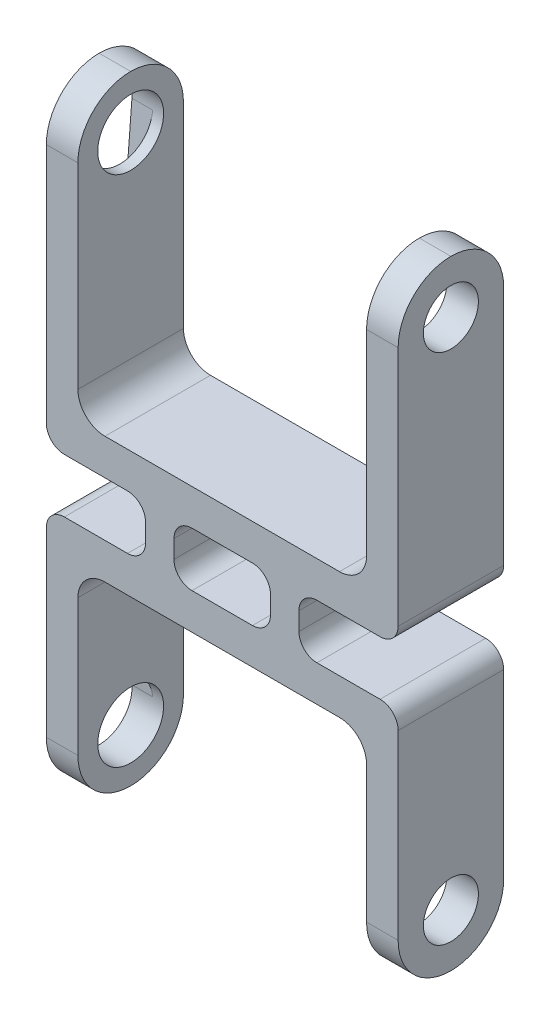
SolidWorks part; units mm, degrees
ref_plane "前视基准面" through (0, 0, 0) normal (0, 0, 1) x (1, 0, 0)
ref_plane "上视基准面" through (0, 0, 0) normal (0, 1, 0) x (1, 0, 0)
ref_plane "右视基准面" through (0, 0, 0) normal (1, 0, 0) x (0, 0, -1)
sketch "草图1" plane through (0, 0, 0) normal (0, 0, 1) x (1, 0, 0)
  line L0 (0, 0) -> (0, -28)
  line L1 (0, -28) -> (3.5, -28)
  line L2 (3.5, -28) -> (3.5, -4)
  line L3 (3.5, -4) -> (35.5, -4)
  line L4 (35.5, -4) -> (35.5, -28)
  line L5 (35.5, -28) -> (39, -28)
  line L6 (39, -28) -> (39, 0)
  line L7 (39, 0) -> (28, 0)
  line L8 (28, 0) -> (28, 6)
  line L9 (28, 6) -> (39, 6)
  line L10 (39, 6) -> (39, 40.6)
  line L11 (39, 40.6) -> (35.5, 40.6)
  line L12 (35.5, 40.6) -> (35.5, 10)
  line L13 (35.5, 10) -> (3.5, 10)
  line L14 (3.5, 10) -> (3.5, 40.6)
  line L15 (3.5, 40.6) -> (0, 40.6)
  line L16 (0, 40.6) -> (0, 6)
  line L17 (0, 6) -> (11, 6)
  line L18 (11, 6) -> (11, 0)
  line L19 (11, 0) -> (0, 0)
  line L20 (0, 3) -> (38, 3) construction
  line L21 (19.5, 4.7421) -> (19.5, 35.9741) construction
  line L22 (11, 3) -> (28, 3) construction
  line L24 (14.15, 0) -> (24.85, 0)
  line L25 (14.15, 0) -> (14.15, 6)
  line L26 (14.15, 6) -> (24.85, 6)
  line L27 (24.85, 0) -> (24.85, 6)
  line L28 (14.15, 0) -> (24.85, 6) construction
  line L29 (14.15, 6) -> (24.85, 0) construction
  point P27 (19.5, 3)
  dimension "D1" = 32
  dimension "D2" = 39
  dimension "D3" = 17
  dimension "D4" = 34.6
  dimension "D5" = 28
  dimension "D6" = 4
  dimension "D7" = 4
  dimension "D8" = 6
  dimension "D9" = 10.7
extrude "凸台-拉伸1" add sketch "草图1" along normal blind 11.7
sketch "草图2" plane through (0, 0, 0) normal (-1, 0, 0) x (0, 0, 1)
  line L0 (5.85, -26) -> (5.85, -9.2381) construction
  line L1 (-6.1344, -22.15) -> (24.0866, -22.15) construction
  line L2 (3.4574, -6.0119) -> (2.2112, -21.8639)
  line L3 (8.2426, -6.0119) -> (9.4888, -21.8639)
  line L4 (0, 0) -> (0, -28)
  line L5 (0, -28) -> (11.7, -28)
  line L6 (11.7, -28) -> (11.7, 0)
  line L7 (11.7, 0) -> (0, 0)
  line L8 (0, 0) -> (0, -28)
  line L9 (0, -28) -> (11.7, -28)
  line L10 (11.7, -28) -> (11.7, 0)
  line L11 (11.7, 0) -> (0, 0)
  line L12 (-23.7504, 6.3) -> (47.2395, 6.3) construction
  line L13 (3.4574, 18.6119) -> (2.2112, 34.4639)
  line L14 (8.2426, 18.6119) -> (9.4888, 34.4639)
  line L16 (11.7, 40.6) -> (0, 40.6) construction
  circle A0 centre (5.85, -22.15) radius 3.65
  arc A1 (8.2426, -6.0119) -> (3.4574, -6.0119) centre (5.85, -6.2) ccw
  arc A2 (8.2426, 18.6119) -> (3.4574, 18.6119) centre (5.85, 18.8) cw
  circle A3 centre (5.85, 34.75) radius 3.65
  point P4 (5.85, -28)
  point P8 (5.85, -22.15)
  point P12 (5.85, -25.8)
  point P16 (5.85, -3.8)
  point P28 (5.85, 38.4)
  dimension "D3" = 22
  dimension "D4" = 4.8
  dimension "D5" = 7.3
  dimension "D2" = 5.85
  dimension "D6" = 5.85
  dimension "D1" = 0
extrude "切除-拉伸1" cut sketch "草图2" against normal blind 18.7 contours A0 region at (0, -22.15, 5.85)
extrude "切除-拉伸2" cut sketch "草图2<3>" against normal blind 2.3 contours L3 A1 L2 A0 region at (0, -12.2589, 5.85)
sketch "草图2<3>" plane through (0, 0, 0) normal (-1, 0, 0) x (0, 0, 1) same geometry as "草图2"
extrude "切除-拉伸3" cut sketch "草图2<4>" against normal blind 15.3 contours A3 region at (0, 34.75, 5.85)
sketch "草图2<4>" plane through (0, 0, 0) normal (-1, 0, 0) x (0, 0, 1) same geometry as "草图2"
extrude "切除-拉伸4" cut sketch "草图2<5>" against normal blind 2.3 contours L14 A3 L13 A2 region at (0, 24.8589, 5.85)
sketch "草图2<5>" plane through (0, 0, 0) normal (-1, 0, 0) x (0, 0, 1) same geometry as "草图2"
fillet "圆角1" radius 2 1 edges at (0, 6, 5.85) type face fillet first side face at (5.5, 6, 5.85) second side face at (0, 26.969, 5.85)
fillet "圆角2" radius 2 1 edges at (39, 6, 5.85) type face fillet first side face at (39, 23.3, 5.85) second side face at (33.5, 6, 5.85)
fillet "圆角3" radius 2 1 edges at (39, 0, 5.85) type face fillet first side face at (33.5, 0, 5.85) second side face at (39, -14, 5.85)
fillet "圆角4" radius 2 1 edges at (0, 0, 5.85) type face fillet first side face at (5.5, 0, 5.85) second side face at (0, -14, 5.85)
fillet "圆角5" radius 5.85 1 edges at (1.75, -28, 11.7) type face fillet first side face at (19.5, 4.1, 11.7) second side face at (1.75, -28, 5.85)
fillet "圆角6" radius 5.85 1 edges at (1.75, -28, 0) type face fillet first side face at (19.5, 4.1, 0) second side face at (1.75, -28, 2.925)
fillet "圆角7" radius 5.85 1 edges at (37.25, -28, 0) type face fillet first side face at (37.25, -28, 5.85) second side face at (19.5, 4.5875, 0)
fillet "圆角8" radius 5.85 1 edges at (37.25, -28, 11.7) type face fillet first side face at (19.5, 4.5875, 11.7) second side face at (37.25, -28, 8.775)
fillet "圆角9" radius 5.85 1 edges at (37.25, 40.6, 11.7) type face fillet first side face at (19.5, 5.075, 11.7) second side face at (37.25, 40.6, 5.85)
fillet "圆角10" radius 5.85 1 edges at (37.25, 40.6, 0) type face fillet first side face at (19.5, 5.075, 0) second side face at (37.25, 40.6, 2.925)
fillet "圆角11" radius 5.85 1 edges at (1.75, 40.6, 0) type face fillet first side face at (19.5, 4.5875, 0) second side face at (1.75, 40.6, 5.85)
fillet "圆角12" radius 5.85 1 edges at (1.75, 40.6, 11.7) type face fillet first side face at (1.75, 40.6, 8.775) second side face at (19.5, 4.5875, 11.7)
fillet "圆角13" radius 2 1 edges at (28, 6, 5.85) type face fillet first side face at (32.5, 6, 5.85) second side face at (28, 3, 5.85)
fillet "圆角14" radius 2 1 edges at (28, 0, 5.85) type face fillet first side face at (28, 2, 5.85) second side face at (32.5, 0, 5.85)
fillet "圆角15" radius 2 1 edges at (11, 6, 5.85) type face fillet first side face at (6.5, 6, 5.85) second side face at (11, 3, 5.85)
fillet "圆角16" radius 2 1 edges at (11, 0, 5.85) type face fillet first side face at (11, 2, 5.85) second side face at (6.5, 0, 5.85)
fillet "圆角17" radius 2 1 edges at (24.85, 6, 5.85) type face fillet first side face at (19.5, 6, 5.85) second side face at (24.85, 3, 5.85)
fillet "圆角18" radius 2 1 edges at (24.85, 0, 5.85) type face fillet first side face at (24.85, 2, 5.85) second side face at (19.5, 0, 5.85)
fillet "圆角19" radius 2 1 edges at (14.15, 6, 5.85) type face fillet first side face at (18.5, 6, 5.85) second side face at (14.15, 3, 5.85)
fillet "圆角20" radius 2 1 edges at (14.15, 0, 5.85) type face fillet first side face at (18.5, 0, 5.85) second side face at (14.15, 2, 5.85)
sketch "草图3" plane through (39, 0, 0) normal (1, 0, 0) x (0, 0, -1)
  circle A0 centre (-5.85, -22.15) radius 3.65 construction
  circle A1 centre (-5.85, 34.75) radius 3.65 construction
  circle A2 centre (-5.85, -22.15) radius 3.65 construction
  circle A3 centre (-5.85, 34.75) radius 3.65 construction
  circle A4 centre (-5.85, 34.75) radius 3.05
  circle A5 centre (-5.85, -22.15) radius 3.05
  dimension "D1" = 6.1
extrude "切除-拉伸5" cut sketch "草图3" against normal blind 10
fillet "圆角21" radius 3 1 edges at (3.5, -4, 5.85) type face fillet first side face at (19.5, -4, 5.85) second side face at (3.5, -22.15, 9.5)
fillet "圆角22" radius 3 1 edges at (35.5, -4, 5.85) type face fillet first side face at (21, -4, 5.85) second side face at (35.5, -22.15, 2.8)
fillet "圆角23" radius 3 1 edges at (35.5, 10, 5.85) type face fillet first side face at (35.5, 37.8, 5.85) second side face at (19.5, 10, 5.85)
fillet "圆角24" radius 3 1 edges at (3.5, 10, 5.85) type face fillet first side face at (3.5, 31.1, 5.85) second side face at (18, 10, 5.85)
